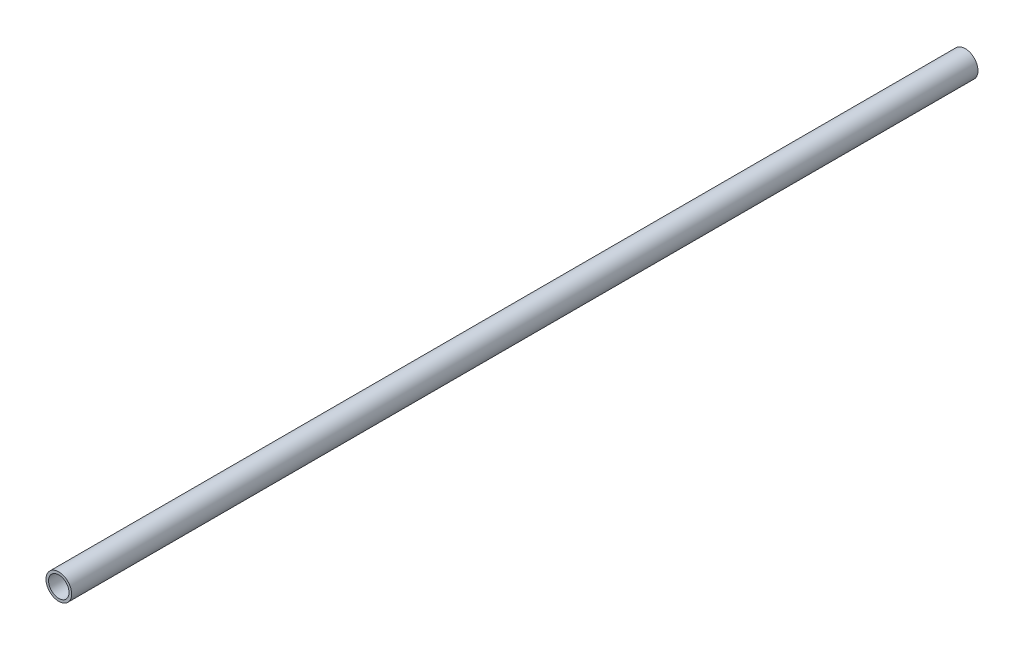
SolidWorks part; units mm, degrees
ref_plane "Front Plane" through (0, 0, 0) normal (0, 0, 1) x (1, 0, 0)
ref_plane "Top Plane" through (0, 0, 0) normal (0, 1, 0) x (1, 0, 0)
ref_plane "Right Plane" through (0, 0, 0) normal (1, 0, 0) x (0, 0, -1)
sketch "Sketch1" plane through (0, 0, 0) normal (0, 0, 1) x (1, 0, 0)
  circle A0 centre (0, 0) radius 16.7005
  circle A1 centre (0, 0) radius 13.3223
  dimension "D1" = 33.401
  dimension " 0.493" = 26.6446
extrude "Boss-Extrude1" add sketch "Sketch1" along normal blind 1181.1
